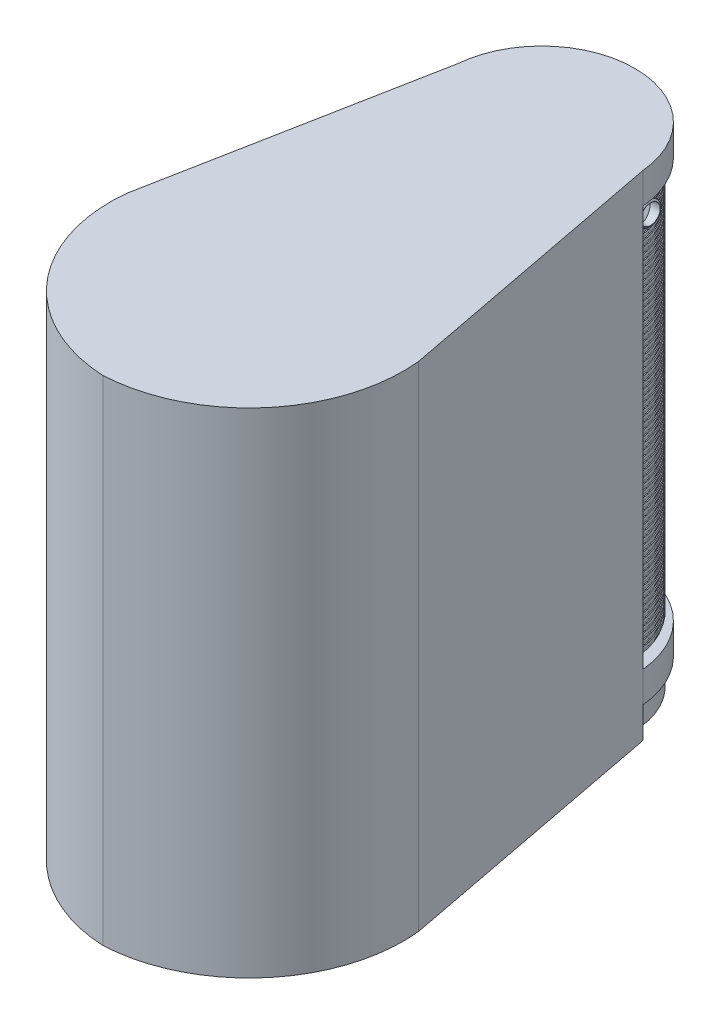
SolidWorks part; units mm, degrees
ref_plane "Front Plane" through (0, 0, 0) normal (0, 0, 1) x (1, 0, 0)
ref_plane "Top Plane" through (0, 0, 0) normal (0, 1, 0) x (1, 0, 0)
ref_plane "Right Plane" through (0, 0, 0) normal (1, 0, 0) x (0, 0, -1)
sketch "Sketch1" plane through (0, 0, 0) normal (0, 1, 0) x (1, 0, 0)
  line L1 (0, 0) -> (0, 298.1608) construction
  line L2 (0, 0) -> (0, -139.7) construction
  line L4 (-119.9973, 0) -> (-76.2, 228.6)
  line L6 (0, 228.6) -> (-76.2, 228.6) construction
  line L7 (0, 298.1608) -> (0, -139.7) construction
  line L8 (0, 0) -> (-119.9973, 0) construction
  line L9 (119.9973, 0) -> (76.2, 228.6)
  arc A0 (-76.2, 228.6) -> (0, 298.1608) centre (-0.2897, 221.9613) cw
  arc A2 (-119.9973, 0) -> (0, -139.7) centre (6.35, -12.8588) ccw
  arc A3 (119.9973, 0) -> (0, -139.7) centre (-6.35, -12.8588) cw
  arc A4 (76.2, 228.6) -> (0, 298.1608) centre (0.2897, 221.9613) ccw
  point P4 (0, 0)
  dimension "D8" = 76.2
  dimension "D6" = 76.2
  dimension "D2" = 127
  dimension "D1" = 228.6
  dimension "D3" = 139.7
  dimension "D4" = 69.5608
  dimension "D5" = 119.9973
extrude "Base" add sketch "Sketch1" against normal blind 406.4
ref_plane "Pod trash" through (0, -25.4, 0) normal (0, 1, 0) x (1, 0, 0)
sketch "Sketch5" plane through (0, -25.4, 0) normal (0, 1, 0) x (1, 0, 0)
  line L0 (-76.2, 228.6) -> (76.2, 228.6)
  arc A0 (-76.2, 228.6) -> (76.2, 228.6) centre (0, 225.4869) cw
  dimension "D2" = 76.2636
  dimension "D1" = 152.4
extrude "Cut for pod trash" cut sketch "Sketch5" against normal blind 330.2
ref_plane "water connection" through (0, -381, 0) normal (0, 1, 0) x (1, 0, 0)
sketch "Sketch7" plane through (0, -381, 0) normal (0, 1, 0) x (1, 0, 0)
  line L0 (-76.2, 228.6) -> (76.2, 228.6)
  arc A0 (-76.2, 228.6) -> (76.2, 228.6) centre (0, 231.4491) cw
  dimension "D2" = 76.2532
  dimension "D1" = 152.4
extrude "water and cord" cut sketch "Sketch7" against normal blind 330.2
sketch "Sketch10" plane through (0, -381, 0) normal (0, -1, 0) x (1, 0, 0)
  line L0 (0, -228.6) -> (0, -298.1608) construction
  line L2 (-76.2, -228.6) -> (76.2, -228.6) construction
  line L3 (0, -263.3804) -> (-89.4641, -263.3804) construction
  line L4 (66.04, -229.87) -> (-66.04, -229.87)
  arc A1 (-66.04, -229.87) -> (66.04, -229.87) centre (0, -229.87) ccw
  point P11 (0, -229.87)
  dimension "D3" = 66.04
  dimension "D5" = 229.87
  dimension "D1" = 69.5608
  dimension "D2" = 89.4641
  dimension "D4" = 132.08
extrude "power" add sketch "Sketch10" along normal blind 25.4
sketch "Sketch11" plane through (0, -355.6, 0) normal (0, 1, 0) x (1, 0, 0)
  line L0 (-66.04, 229.87) -> (66.04, 229.87)
  arc A0 (-66.04, 229.87) -> (66.04, 229.87) centre (0, 229.87) cw
  dimension "D2" = 66.04
  dimension "D1" = 132.08
extrude "pod trash bin" add sketch "Sketch11" along normal blind 327.66 separate body
sketch "Sketch14" plane through (0, 0, 0) normal (1, 0, 0) x (0, 0, -1)
  line L0 (229.87, -27.94) -> (245.11, -27.94) construction
  line L1 (295.91, -27.94) -> (229.87, -27.94) construction
  line L2 (245.11, -27.94) -> (245.11, -44.45) construction
  circle A0 centre (245.11, -44.45) radius 9.525
  dimension "D3" = 19.05
  dimension "D1" = 15.24
  dimension "D2" = 16.51
sketch "Sketch15" plane through (0, 0, -229.87) normal (0, 0, 1) x (1, 0, 0)
  line L0 (66.04, -355.6) -> (65.278, -355.6)
  line L1 (-66.04, -355.6) -> (66.04, -355.6) construction
  line L2 (65.278, -355.6) -> (65.278, -353.06)
  line L3 (65.278, -353.06) -> (66.04, -353.06)
  line L4 (66.04, -27.94) -> (66.04, -355.6) construction
  line L5 (66.04, -353.06) -> (66.04, -355.6)
  line L6 (0, 0) -> (0, -397.6051) construction
  dimension "D1" = 397.6051
  dimension "D2" = 2.54
  dimension "D3" = 0.762
revolve "Cut-Revolve1" cut sketch "Sketch15" angle 360 about L6
pattern_linear "LPattern3" count 68 spacing 4.826 along (0, 1, 0) of "Cut-Revolve1"
extrude "Hole extrude" add sketch "Sketch14" along normal mid plane 132.08
fillet "Fillet4" radius 1.27 2 edges at (66.04, -44.45, -254.635) (-66.04, -44.45, -254.635)
sketch "Sketch17" plane through (66.04, 0, 0) normal (1, 0, 0) x (0, 0, -1)
  line L0 (245.11, -36.195) -> (245.11, -44.45) construction
  circle A1 centre (245.11, -44.45) radius 8.255 construction
  circle A2 centre (245.11, -44.45) radius 8.001
  dimension "D2" = 16.002
  dimension "D1" = 8.255
extrude "Hole cut" cut sketch "Sketch17" against normal through all
sketch "Sketch18" plane through (0, -27.94, 0) normal (0, 1, 0) x (1, 0, 0)
  line L0 (62.23, 233.2036) -> (-62.23, 233.2036)
  arc A1 (-62.23, 233.2036) -> (62.23, 233.2036) centre (0, 229.8201) cw
  point P3 (0, 233.2036)
  dimension "D1" = 62.3219
  dimension "D2" = 124.46
  dimension "D3" = 3.3336
extrude "Inside" cut sketch "Sketch18" against normal blind 317.5
